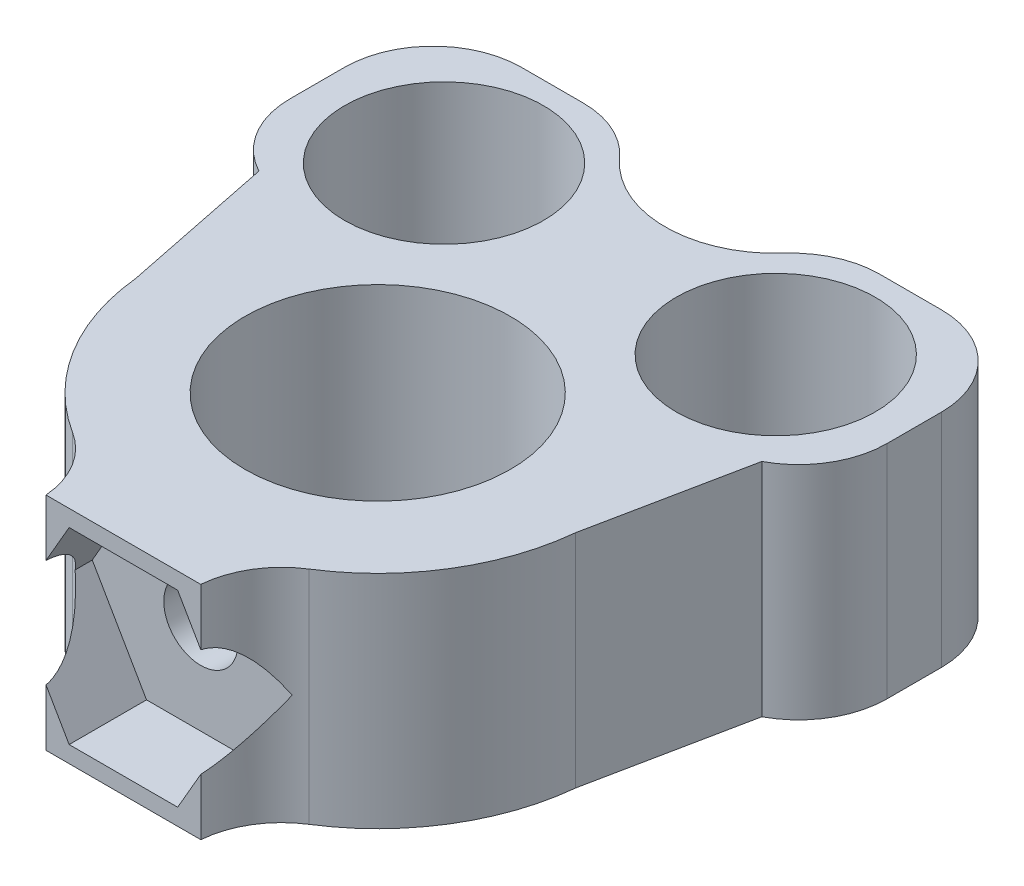
SolidWorks part; units mm, degrees
ref_plane "Alzado" through (0, 0, 0) normal (0, 0, 1) x (1, 0, 0)
ref_plane "Planta" through (0, 0, 0) normal (0, 1, 0) x (1, 0, 0)
ref_plane "Vista lateral" through (0, 0, 0) normal (1, 0, 0) x (0, 0, -1)
sketch "Croquis1" plane through (0, 0, 0) normal (0, 1, 0) x (1, 0, 0)
  line L0 (-13.5, 16) -> (-4.5826, 16)
  line L1 (-13.5, 16) -> (13.5, 16) construction
  line L2 (-13.5, 16) -> (-13.5, 6)
  line L3 (-13.5, 6) -> (13.5, 6)
  line L4 (13.5, 16) -> (13.5, 6)
  line L5 (4.5826, 16) -> (13.5, 16)
  circle A0 centre (0, 0) radius 6
  circle A1 centre (0, 0) radius 10
  arc A2 (-4.5826, 16) -> (4.5826, 16) centre (0, 18) ccw
  point P8 (0, 6)
  point P13 (0, 16)
  dimension "D1" = 12
  dimension "D2" = 4
  dimension "D5" = 5
  dimension "D3" = 27
  dimension "D4" = 10
  dimension "D6" = 2
extrude "Saliente-Extruir1" add sketch "Croquis1" along normal blind 10 contours A1 L3 L4 L1 L2 | L3 A1 | L3 A1 A0 region at (0, 0, -11.3705) region at (0, 0, -7.6311) region at (-4, 0, -5.7439)
sketch "Croquis2" plane through (0, 10, 0) normal (0, 1, 0) x (1, 0, 0)
  line L0 (-7.5, 10.5) -> (7.5, 10.5) construction
  circle A0 centre (-7.5, 10.5) radius 4.5
  circle A1 centre (7.5, 10.5) radius 4.5
  point P4 (0, 10.5)
  dimension "D1" = 9
  dimension "D2" = 15
  dimension "D3" = 10.5
extrude "Cortar-Extruir1" cut sketch "Croquis2" against normal blind 10
chamfer "Chaflán1" distance 10 angle 45 2 edges at (-8, 5, -6) (8, 5, -6) first distance on face at (0, 5, 2)
sketch "Croquis3" plane through (0, 0, 0) normal (0, 1, 0) x (1, 0, 0)
  line L1 (-3.5, -8.5) -> (3.5, -8.5)
  line L2 (-3.5, -8.5) -> (-3.5, -11.5)
  line L3 (-3.5, -11.5) -> (3.5, -11.5)
  line L4 (3.5, -8.5) -> (3.5, -11.5)
  line L5 (-3.5, -8.5) -> (3.5, -11.5) construction
  line L6 (-3.5, -11.5) -> (3.5, -8.5) construction
  arc A0 (-9.9499, -1) -> (9.9499, -1) centre (0, 0) ccw construction
  point P0 (0, -10)
  dimension "D1" = 7
  dimension "D2" = 3
extrude "Saliente-Extruir2" add sketch "Croquis3" along normal up to surface (10 mm away) up to face at (7.5, 10, -6)
sketch "Croquis4" plane through (0, 0, 11.5) normal (0, 0, 1) x (1, 0, 0)
  line L0 (3.5, 10) -> (3.5, 0) construction
  circle A0 centre (0, 5) radius 1.675
  point P6 (3.5, 5)
  dimension "D1" = 3.35
extrude "Cortar-Extruir2" cut sketch "Croquis4" against normal blind 10
fillet "Redondeo2" radius 4 8 edges at (13.5, 5, -16) (13.5, 5, -6) (-13.5, 5, -6) (-13.5, 5, -16) (-3.5, 5, 9.3675) (3.5, 5, 9.3675) (4.5826, 5, -16) (-4.5826, 5, -16)
sketch "Croquis5" plane through (0, 0, 11.5) normal (0, 0, 1) x (1, 0, 0)
  line L1 (4.9075, 5) -> (2.4537, 9.25)
  line L2 (2.4537, 9.25) -> (-2.4537, 9.25)
  line L3 (-2.4537, 9.25) -> (-4.9075, 5)
  line L4 (-4.9075, 5) -> (-2.4537, 0.75)
  line L5 (-2.4537, 0.75) -> (2.4537, 0.75)
  line L6 (2.4537, 0.75) -> (4.9075, 5)
  circle A0 centre (0, 5) radius 4.25 construction
  dimension "D1" = 8.5
extrude "Cortar-Extruir3" cut sketch "Croquis5" against normal blind 3.5
